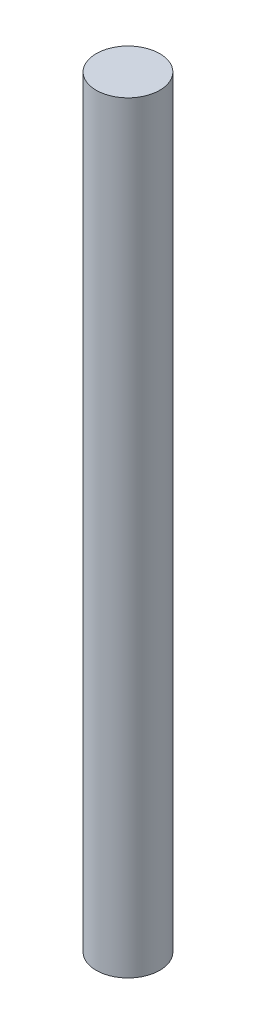
SolidWorks part; units mm, degrees
ref_plane "Front Plane" through (0, 0, 0) normal (0, 0, 1) x (1, 0, 0)
ref_plane "Top Plane" through (0, 0, 0) normal (0, 1, 0) x (1, 0, 0)
ref_plane "Right Plane" through (0, 0, 0) normal (1, 0, 0) x (0, 0, -1)
sketch "Bar face" plane through (0, 0, 0) normal (0, 1, 0) x (1, 0, 0)
  circle A0 centre (0, 0) radius 2.5
  dimension "D1" = 5
extrude "Bar extrude" add sketch "Bar face" along normal blind 60
